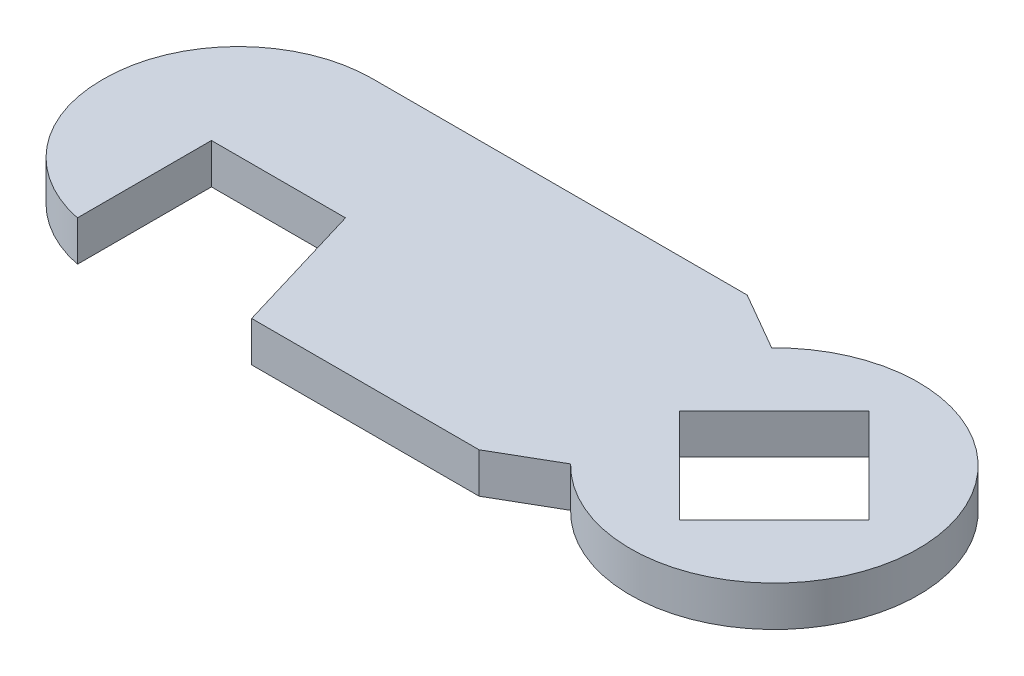
SolidWorks part; units mm, degrees
ref_plane "前视基准面" through (0, 0, 0) normal (0, 0, 1) x (1, 0, 0)
ref_plane "上视基准面" through (0, 0, 0) normal (0, 1, 0) x (1, 0, 0)
ref_plane "右视基准面" through (0, 0, 0) normal (1, 0, 0) x (0, 0, -1)
sketch "草图2" plane through (0, 0, 0) normal (0, 1, 0) x (1, 0, 0)
  line L0 (-12.0316, -10) -> (-7.7015, -7.5)
  line L1 (-50, 10) -> (-12.0316, 10)
  line L2 (-50, 10) -> (-50, -10)
  line L3 (-50, -10) -> (-12.0316, -10)
  line L4 (-59.6233, 0) -> (20.4513, 0) construction
  line L5 (-12.0316, 10) -> (-7.7015, 7.5)
  arc A0 (-7.7015, -7.5) -> (-7.7015, 7.5) centre (0, 0) ccw
  dimension "D3" = 30
  dimension "D4" = 21.5
  dimension "D5" = 5
  dimension "D1" = 50
  dimension "D2" = 20
extrude "凸台-拉伸1" add sketch "草图2" along normal blind 3
sketch "草图3" plane through (0, 3, 0) normal (0, 1, 0) x (1, 0, 0)
  line L0 (0, 0) -> (0, 13.5966) construction
  line L1 (0, 7.0711) -> (-7.0711, 0)
  line L2 (-7.0711, 0) -> (0, -7.0711)
  line L3 (0, -7.0711) -> (7.0711, 0)
  line L4 (7.0711, 0) -> (0, 7.0711)
  circle A0 centre (0, 0) radius 5 construction
  dimension "D1" = 10
extrude "切除-拉伸1" cut sketch "草图3" against normal through all
sketch "草图5" plane through (0, 3, 0) normal (0, 1, 0) x (1, 0, 0)
  line L0 (-42, -10) -> (-42, 0)
  line L1 (-50, -10) -> (-12.0316, -10) construction
  line L2 (-42, 0) -> (-32, 0)
  line L3 (-32, 0) -> (-29, -10)
  line L4 (-42, -10) -> (-29, -10)
  dimension "D1" = 13
  dimension "D2" = 10
  dimension "D3" = 10
  dimension "D4" = 42
extrude "切除-拉伸3" cut sketch "草图5" against normal blind 10
fillet "圆角1" radius 10 2 edges at (-50, 1.5, -10) (-50, 1.5, 10)
